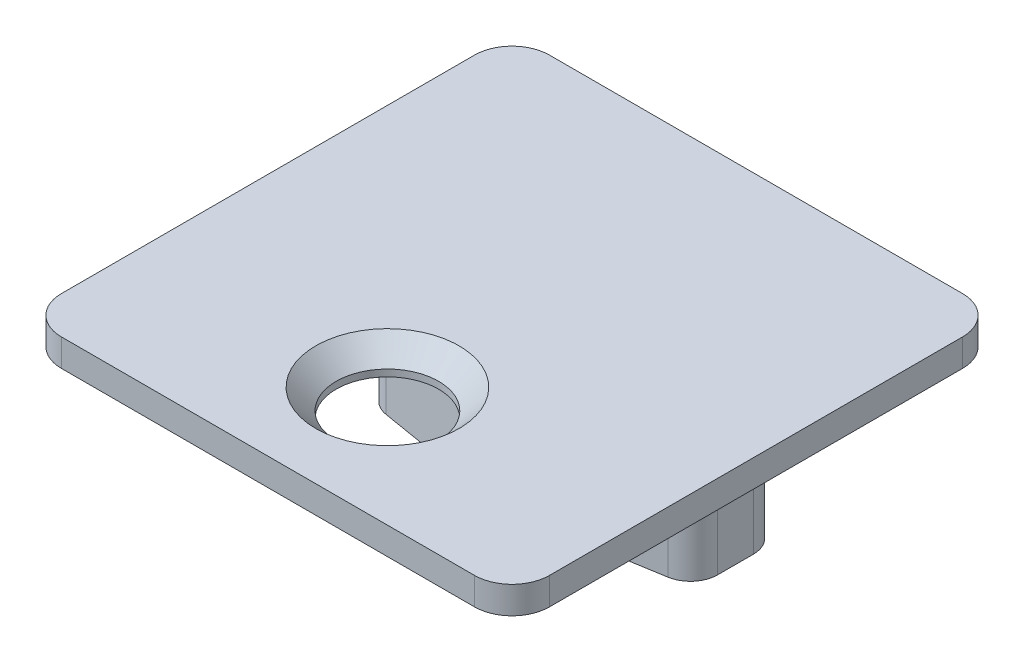
SolidWorks part; units mm, degrees
ref_plane "Ebene vorne" through (0, 0, 0) normal (0, 0, 1) x (1, 0, 0)
ref_plane "Ebene oben" through (0, 0, 0) normal (0, 1, 0) x (1, 0, 0)
ref_plane "Ebene rechts" through (0, 0, 0) normal (1, 0, 0) x (0, 0, -1)
sketch "Skizze1" plane through (0, 0, 0) normal (0, 1, 0) x (1, 0, 0)
  line L0 (-15.125, 17.875) -> (15.125, 17.875)
  line L1 (-15.125, 16.875) -> (15.125, 16.875)
  line L2 (-16.875, 15.125) -> (-16.875, -15.125)
  line L3 (-15.125, -16.875) -> (15.125, -16.875)
  line L4 (16.875, 15.125) -> (16.875, -15.125)
  line L5 (-16.875, 16.875) -> (16.875, -16.875) construction
  line L6 (-16.875, -16.875) -> (16.875, 16.875) construction
  line L7 (17.875, 15.125) -> (17.875, -15.125)
  line L8 (-15.125, -17.875) -> (15.125, -17.875)
  line L9 (-17.875, 15.125) -> (-17.875, -15.125)
  line L10 (0, 9.375) -> (0, -0.625) construction
  line L11 (-16.875, 11.375) -> (16.875, 11.375)
  line L12 (-16.875, 11.375) -> (-16.875, -2.625)
  line L13 (-16.875, -2.625) -> (16.875, -2.625)
  line L14 (16.875, 11.375) -> (16.875, -2.625)
  line L15 (-10, 9.375) -> (10, 9.375)
  line L16 (-12, 7.375) -> (-12, 1.375)
  line L17 (-10, -0.625) -> (10, -0.625)
  line L18 (12, 7.375) -> (12, 1.375)
  line L19 (0, -0.625) -> (0, -16.875) construction
  line L20 (-12, 7.375) -> (0, 9.375)
  line L21 (0, 9.375) -> (12, 7.375)
  line L22 (-12, 1.375) -> (0, -0.625)
  line L23 (0, -0.625) -> (12, 1.375)
  line L24 (-10.5, 6.1043) -> (-10.5, 2.6457)
  line L25 (-10.5, 2.6457) -> (0, 0.8957)
  line L26 (0, 0.8957) -> (10.5, 2.6457)
  line L27 (10.5, 6.1043) -> (10.5, 2.6457)
  line L28 (0, 7.8543) -> (10.5, 6.1043)
  line L29 (-10.5, 6.1043) -> (0, 7.8543)
  arc A0 (-16.875, -15.125) -> (-15.125, -16.875) centre (-15.125, -15.125) ccw
  arc A1 (15.125, -16.875) -> (16.875, -15.125) centre (15.125, -15.125) ccw
  arc A2 (15.125, 16.875) -> (16.875, 15.125) centre (15.125, 15.125) cw
  arc A3 (-15.125, 16.875) -> (-16.875, 15.125) centre (-15.125, 15.125) ccw
  arc A4 (15.125, 17.875) -> (17.875, 15.125) centre (15.125, 15.125) cw
  arc A5 (15.125, -17.875) -> (17.875, -15.125) centre (15.125, -15.125) ccw
  arc A6 (-17.875, -15.125) -> (-15.125, -17.875) centre (-15.125, -15.125) ccw
  arc A7 (-15.125, 17.875) -> (-17.875, 15.125) centre (-15.125, 15.125) ccw
  arc A8 (-12, 1.375) -> (-10, -0.625) centre (-10, 1.375) ccw
  arc A9 (10, -0.625) -> (12, 1.375) centre (10, 1.375) ccw
  arc A10 (10, 9.375) -> (12, 7.375) centre (10, 7.375) cw
  arc A11 (-10, 9.375) -> (-12, 7.375) centre (-10, 7.375) ccw
  circle A12 centre (0, -9.125) radius 3.75
  point P0 (0, 0)
  point P44 (12, -0.625)
  point P47 (12, 9.375)
  point P50 (-12, 9.375)
  dimension "D3" = 1.75
  dimension "D10" = 2
  dimension "D11" = 7.5
  dimension "D12" = 8.5
  dimension "D1" = 33.75
  dimension "D2" = 33.75
  dimension "D5" = 5.5
  dimension "D6" = 14
  dimension "D7" = 10
  dimension "D8" = 24
  dimension "D9" = 2
  dimension "D4" = 1
  dimension "D13" = 1.5
extrude "Aufsatz-Linear austragen1" add sketch "Skizze1" along normal blind 2 contours L0 A7 L9 A6 L8 A5 L7 A4 A3 L1 A2 L4 A1 L3 A0 L2 | L3 A1 L4 L13 L2 A0 A12 | L2 L13 L4 L11 A11 L15 A10 L18 A9 L17 A8 L16 | L22 L23 L18 L21 L20 L16 L24 L29 L28 L27 L26 L25 | L29 L24 L25 L26 L27 L28 | L22 A8 L17 | L17 A9 L23 | A10 L15 L21 | L15 A11 L20 | L1 A3 L2 L11 L4 A2 region at (0, 0, -17.3694) region at (0, 0, -14.1082) region at (0, 0, -11.0096) region at (0, 0, 2.9914) region at (-7.7262, 0, -8.6914) region at (5.9573, 0, -8.1185) region at (7.7262, 0, -8.6914) region at (-7.7262, 0, -0.0586) region at (7.7262, 0, -0.0586) region at (0, 0, -4.375)
extrude "Aufsatz-Linear austragen2" add sketch "Skizze1<6>" against normal blind 10 contours L22 L23 L18 L21 L20 L16 L24 L29 L28 L27 L26 L25 region at (5.9573, 0, -8.1185)
sketch "Skizze1<6>" plane through (0, 0, 0) normal (0, 1, 0) x (1, 0, 0) same geometry as "Skizze1"
fillet "Verrundung1" radius 2 6 edges at (0, -5, -9.375) (0, -5, 0.625) (12, -5, -1.375) (12, -5, -7.375) (-12, -5, -1.375) (-12, -5, -7.375)
chamfer "Fase2" distance 1.5 angle 45 1 edges at (0, 2, 12.875)
